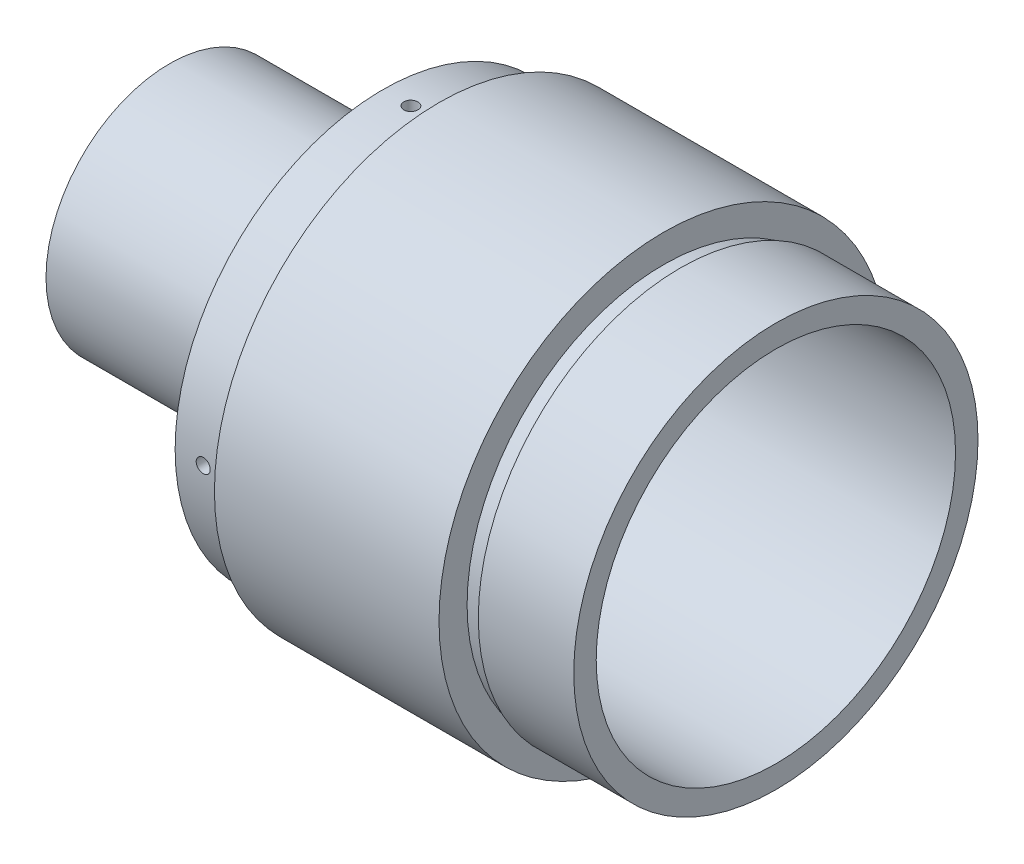
SolidWorks part; units mm, degrees
ref_plane "Ön Düzlem" through (0, 0, 0) normal (0, 0, 1) x (1, 0, 0)
ref_plane "Üst Düzlem" through (0, 0, 0) normal (0, 1, 0) x (1, 0, 0)
ref_plane "Sağ Düzlem" through (0, 0, 0) normal (1, 0, 0) x (0, 0, -1)
ref_axis "Eksen1" through (-88.99, 0, 0) along (1, 0, 0)
sketch "Çizim1" plane through (0, 0, 0) normal (0, 0, 1) x (1, 0, 0)
  line L2 (-60, 40) -> (-60, 37)
  line L3 (-60, 37) -> (-70, 37)
  line L4 (-70, 37) -> (-70, 22)
  line L10 (-57, 18.2) -> (-57, 32)
  line L11 (-57, 32) -> (0, 32)
  line L12 (0, 32) -> (0, 36)
  line L14 (-20, 40) -> (-60, 40)
  line L20 (-20, 40) -> (-20, 35)
  line L21 (-20, 35) -> (-17, 35)
  line L22 (-17, 35) -> (-17, 36)
  line L23 (-17, 36) -> (0, 36)
  line L24 (-57, 18.2) -> (-106, 18.2)
  line L25 (-106, 18.2) -> (-106, 4)
  line L26 (-106, 4) -> (-108, 4)
  line L27 (-108, 4) -> (-108, 22)
  line L28 (-70, 22) -> (-108, 22)
  dimension "D1" = 4
revolve "Döndür1" add sketch "Çizim1" angle 360 about axis through (-88.99, 0, 0) along (1, 0, 0)
sketch "Çizim12" plane through (0, 0, 0) normal (1, 0, 0) x (0, 0, -1)
  circle A0 centre (12.5, 0) radius 1.6
extrude "Kes-Ekstrüzyon1" cut sketch "Çizim12" against normal through all
pattern_circular "Dairesel Kaplama1" count 6 over 360 about axis through (-88.99, 0, 0) along (1, 0, 0) of "Kes-Ekstrüzyon1"
sketch "Çizim13" plane through (0, 0, 0) normal (0, 0, 1) x (1, 0, 0)
  line L2 (-88.99, 0) -> (88.99, 0) construction
  circle A0 centre (-65, 0) radius 1.25
extrude "Kes-Ekstrüzyon2" cut sketch "Çizim13" along normal blind 10 from offset 27
pattern_circular "Dairesel Kaplama2" count 4 over 360 about axis through (-88.99, 0, 0) along (1, 0, 0) of "Kes-Ekstrüzyon2"
